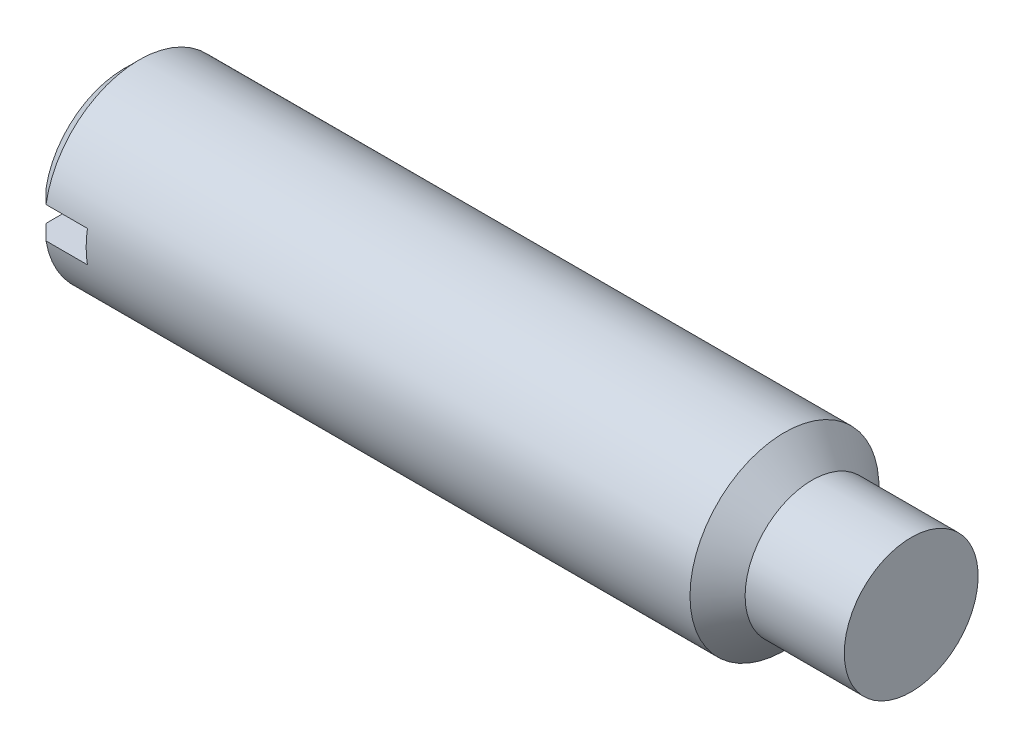
SolidWorks part; units mm, degrees
ref_plane "Front Plane" through (0, 0, 0) normal (0, 0, 1) x (1, 0, 0)
ref_plane "Top Plane" through (0, 0, 0) normal (0, 1, 0) x (1, 0, 0)
ref_plane "Right Plane" through (0, 0, 0) normal (1, 0, 0) x (0, 0, -1)
sketch "BodySke" plane through (0, 0, 0) normal (0, 0, 1) x (1, 0, 0)
  line L0 (0, 0) -> (88.3411, 0) construction
  line L1 (0, 0) -> (0, 5.036)
  line L2 (0, 5.036) -> (0.964, 6)
  line L3 (0.964, 6) -> (41.95, 6)
  line L4 (43.7, 4.25) -> (41.95, 6)
  line L5 (43.7, 4.25) -> (50, 4.25)
  line L6 (50, 0) -> (0, 0)
  line L7 (1.75, 0) -> (1.75, 8.5388) construction
  line L8 (50, 4.25) -> (50, 0)
  line L9 (0, -5.036) -> (0.964, -6) construction
  dimension "Thread_minor" = 10.072
  dimension "Length" = 50
  dimension "Drive_chamfer_angle" = 90
  dimension "Advance" = 1.75
revolve "BaseBody" add sketch "BodySke" angle 360 about L0
cosmetic thread "ThreadCosmetic" [suppressed] parameters "Thread_minor"=10.072
sketch "SlotSke" plane through (0, 0, 0) normal (1, 0, 0) x (0, 0, -1)
  line L0 (-6, 1) -> (6, -1) construction
  line L1 (-6, 1) -> (6, 1)
  line L2 (-6, 1) -> (-6, -1)
  line L3 (-6, -1) -> (6, -1)
  line L4 (6, 1) -> (6, -1)
  dimension "D1" = 12
extrude "Slot" cut sketch "SlotSke" along normal blind 3.6
sketch "ThdSchSke" plane through (0, 0, 0) normal (0, 0, 1) x (1, 0, 0)
  line L0 (0, 0) -> (53.6961, 0) construction
  line L1 (1.6009, 7.1131) -> (1.6009, 6)
  line L2 (1.6009, 7.1131) -> (2.714, 7.1131)
  line L3 (2.714, 7.1131) -> (2.714, 6)
  line L4 (2.714, 6) -> (2.1574, 5.036)
  line L5 (2.1574, 5.036) -> (1.6009, 6)
  dimension "D1" = 1.75
revolve "ThreadSchematic" [suppressed] cut sketch "ThdSchSke" angle 360 about L0
pattern_linear "ThdSchPat" [suppressed] of bodies 115
equation "\"Thread_minor@ThreadCosmetic\" = \"Thread_minor@BodySke\""
equation "\"D1@SlotSke\" = \"Diameter@BodySke\""
equation "\"D1@ThdSchSke\" = \"Advance@BodySke\""
equation "\"Advance@ThdSchPat\" = \"Advance@BodySke\""
equation "\"Tooth_Num@ThdSchPat\" =  int( \"Length@BodySke\" / \"Advance@BodySke\" )  - 1"
